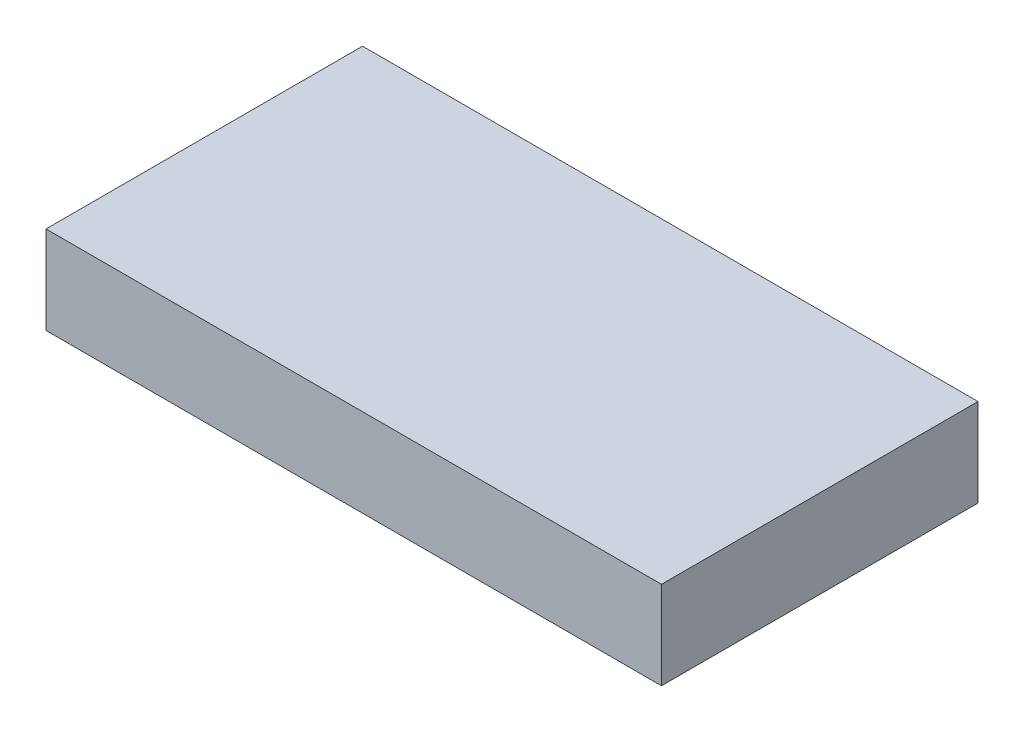
SolidWorks part; units mm, degrees
ref_plane "Front Plane" through (0, 0, 0) normal (0, 0, 1) x (1, 0, 0)
ref_plane "Top Plane" through (0, 0, 0) normal (0, 1, 0) x (1, 0, 0)
ref_plane "Right Plane" through (0, 0, 0) normal (1, 0, 0) x (0, 0, -1)
sketch "Sketch1" plane through (0, 0, 0) normal (0, 1, 0) x (1, 0, 0)
  line L1 (-17.5, 9) -> (17.5, 9)
  line L2 (-17.5, 9) -> (-17.5, -9)
  line L3 (-17.5, -9) -> (17.5, -9)
  line L4 (17.5, 9) -> (17.5, -9)
  line L5 (-17.5, 9) -> (17.5, -9) construction
  line L6 (-17.5, -9) -> (17.5, 9) construction
  point P0 (0, 0)
  dimension "D1" = 35
  dimension "D2" = 18
extrude "Boss-Extrude1" add sketch "Sketch1" along normal blind 5
